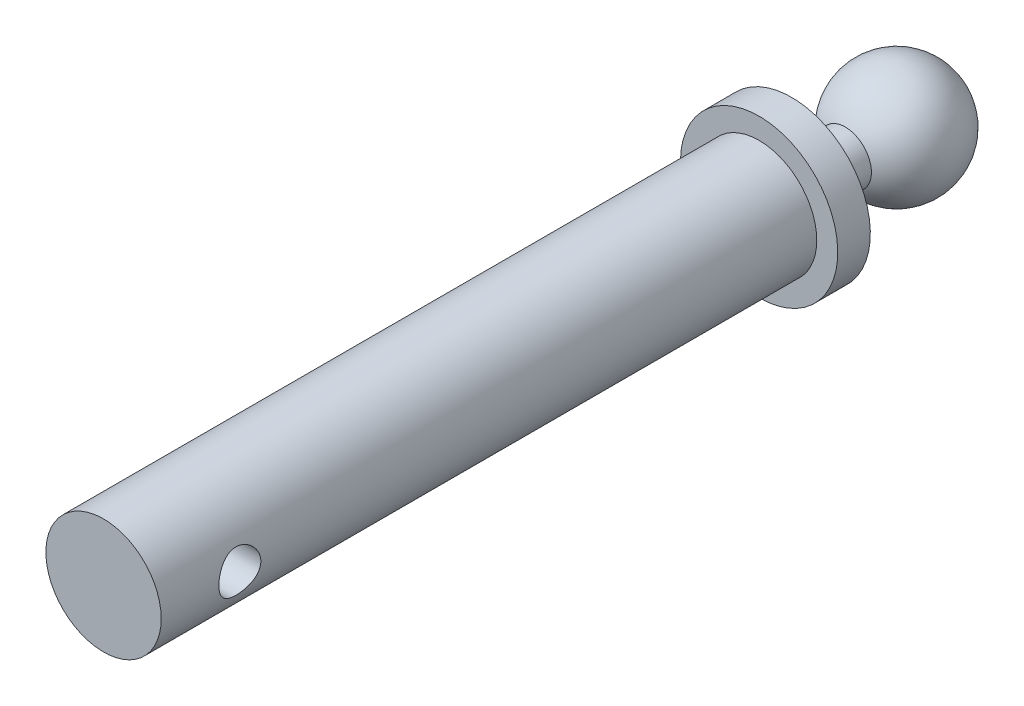
SolidWorks part; units mm, degrees
ref_plane "Plano frontal" through (0, 0, 0) normal (0, 0, 1) x (1, 0, 0)
ref_plane "Plano superior" through (0, 0, 0) normal (0, 1, 0) x (1, 0, 0)
ref_plane "Plano direito" through (0, 0, 0) normal (1, 0, 0) x (0, 0, -1)
sketch "Esboço1" plane through (0, 0, 0) normal (0, 0, 1) x (1, 0, 0)
  line L0 (-15.9999, 0) -> (15.9999, 0) construction
  circle A1 centre (15.9999, 0) radius 5.4973
  dimension "D2" = 10.9947
  dimension "D3" = 15.9999
extrude "Ressalto-extrusão1" add sketch "Esboço1" along normal blind 60 and the other way blind 15
sketch "Esboço2" plane through (0, 0, 0) normal (1, 0, 0) x (0, 0, -1)
  line L0 (-60, 5.4973) -> (-60, -5.4973) construction
  circle A0 centre (-60, 0) radius 4
  dimension "D1" = 8
extrude "Corte-extrusão1" cut sketch "Esboço2" against normal blind 71 and the other way blind 71
sketch "Esboço8" plane through (0, 0, 0) normal (1, 0, 0) x (0, 0, -1)
  circle A2 centre (-52, 0) radius 2
extrude "Corte-extrusão3" cut sketch "Esboço8" along normal through all and the other way through all
sketch "Esboço9" plane through (0, 0, -15) normal (0, 0, -1) x (-1, 0, 0)
  circle A0 centre (-15.9999, 0) radius 7.5
  circle A1 centre (-15.9999, 0) radius 5.4973
  circle A2 centre (-15.9999, 0) radius 5.4973
  dimension "D2" = 15
  dimension "D1" = 0
extrude "Ressalto-extrusão5" add sketch "Esboço9" along normal blind 4 from offset 12 offset against normal yes
sketch "Esboço11" plane through (0, 0, 0) normal (1, 0, 0) x (0, 0, -1)
  line L0 (-56, 0) -> (-56, 5.4973)
  line L1 (-56, 5.4973) -> (-56, -5.4973)
  line L2 (-60, 4) -> (-60, -5.4973)
  line L3 (-60, 5.4973) -> (-60, 4) construction
  line L4 (-60, -5.4973) -> (-60, 5.4973)
  line L5 (-60, -5.4973) -> (3, -5.4973) construction
  line L6 (3, 5.4973) -> (-60, 5.4973) construction
  line L7 (-60, -5.4973) -> (-56, -5.4973)
  line L8 (-56, 5.4973) -> (-60, 5.4973)
  arc A0 (-60, -4) -> (-60, 4) centre (-60, 0) ccw construction
extrude "Corte-extrusão5" cut sketch "Esboço11" along normal through all contours L0 L8 L4 L2 L7 L1 region at (0, 0, 58)
sketch "Esboço12" plane through (0, 0, 56) normal (0, 0, 1) x (1, 0, 0)
  circle A1 centre (15.9999, 0) radius 5.4973
  circle A2 centre (15.9999, 0) radius 5.4973
  dimension "D1" = 0
extrude "Ressalto-extrusão6" add sketch "Esboço12" along normal blind 3.5
sketch "Esboço14" plane through (0, 0, -15) normal (0, 0, -1) x (-1, 0, 0)
  circle A1 centre (-15.9999, 0) radius 5.4973
  circle A2 centre (-15.9999, 0) radius 5.4973
  circle M2 centre (-15.9999, 0) radius 5.4973
  dimension "D1" = 0
extrude "Ressalto-extrusão7" add sketch "Esboço14" along normal blind 6 contours M2 region at (15.9999, 0, -15)
sketch "Esboço16" plane through (0, 0, 0) normal (1, 0, 0) x (0, 0, -1)
  line L1 (-18.895, 5.4973) -> (-18.895, -21.1472) construction
  circle A0 centre (-52, 0) radius 2 construction
  circle A2 centre (14.21, 0) radius 2
  dimension "D1" = 14.21
extrude "Corte-extrusão7" cut sketch "Esboço16" along normal through all and the other way through all
sketch "Esboço17" plane through (0, 0, 0) normal (1, 0, 0) x (0, 0, -1)
  line L0 (19.21, -9.1624) -> (19.21, -5.1185)
  line L1 (9.21, -5.1185) -> (9.21, -9.1624)
  line L2 (9.21, -9.1624) -> (19.21, -9.1624)
  line L3 (19.21, -5.1185) -> (19.21, 5.1185)
  line L4 (9.21, 5.1185) -> (9.21, -5.1185)
  line L5 (19.21, 5.1185) -> (19.21, 9.4973)
  line L6 (19.21, 5.1185) -> (9.21, 5.1185)
  line L7 (9.21, 9.4973) -> (9.21, 5.1185)
  line L8 (19.21, 9.4973) -> (9.21, 9.4973)
  line L9 (9.21, -5.1185) -> (19.21, -5.1185)
  line L10 (9.21, 0) -> (19.21, 0)
  dimension "D1" = 9.21
  dimension "D2" = 9.21
  dimension "D3" = 19.21
  dimension "D4" = 19.21
  dimension "D5" = 5.1185
  dimension "D6" = 9.4973
  dimension "D7" = 9.4973
  dimension "D8" = 5.1185
  dimension "D11" = 9.1624
  dimension "D12" = 9.1624
extrude "Corte-extrusão8" cut sketch "Esboço17" against normal through all and the other way through all contours L10 L4 L9 L3 | L4 L10 L3 L6 region at (0, -2.5593, -14.21) region at (0, 2.5593, -14.21)
sketch "Esboço18" plane through (0, 0, -21) normal (0, 0, -1) x (-1, 0, 0)
  line L0 (-18.0052, 5.1185) -> (-21.4817, 5.1185)
  line L1 (-21.4817, 5.1185) -> (-10.5181, 5.1185)
  line L2 (-18.0052, -5.1185) -> (-13.9946, -5.1185)
  line L3 (-13.9946, 5.1185) -> (-18.0052, 5.1185)
  line L4 (-18.0052, -5.1185) -> (-13.9946, -5.1185)
  line L5 (-13.9946, 5.1185) -> (-18.0052, 5.1185)
  line L6 (-18.0052, -5.1185) -> (-21.4817, -5.1185)
  line L7 (-21.4817, -5.1185) -> (-10.5181, -5.1185)
  circle A1 centre (-15.9999, 0) radius 7.5
  arc A2 (-13.9946, -5.1185) -> (-13.9946, 5.1185) centre (-15.9999, 0) ccw
  arc A3 (-18.0052, 5.1185) -> (-18.0052, -5.1185) centre (-15.9999, 0) ccw
  arc A4 (-13.9946, -5.1185) -> (-13.9946, 5.1185) centre (-15.9999, 0) ccw
  arc A5 (-18.0052, 5.1185) -> (-18.0052, -5.1185) centre (-15.9999, 0) ccw
  circle A6 centre (-15.9999, 0) radius 7.5
  circle M6 centre (-15.9999, 0) radius 5.4973
  dimension "D1" = 0
  dimension "D2" = 0
extrude "Ressalto-extrusão8" add sketch "Esboço18" against normal up to surface (14 mm away) contours L1 A6 L0 M6 | L6 A6 L7 M6 region at (15.9999, 6.1342, -21) region at (15.9999, -6.1342, -21) up to face at (8.4999, 0, -7)
sketch "Esboço19" plane through (0, 0, -21) normal (0, 0, -1) x (-1, 0, 0)
  line L0 (-10.5181, 5.1185) -> (-13.9946, 5.1185) construction
  line L1 (-13.9946, -5.1185) -> (-10.5181, -5.1185) construction
  line L2 (-21.4817, -5.1185) -> (-18.0052, -5.1185) construction
  line L3 (-18.0052, 5.1185) -> (-21.4817, 5.1185) construction
  line L4 (-10.5181, 5.1185) -> (-13.9946, 5.1185)
  line L5 (-13.9946, -5.1185) -> (-10.5181, -5.1185)
  line L6 (-21.4817, -5.1185) -> (-18.0052, -5.1185)
  line L7 (-18.0052, 5.1185) -> (-21.4817, 5.1185)
  arc A0 (-13.9946, -5.1185) -> (-13.9946, 5.1185) centre (-15.9999, 0) ccw construction
  arc A1 (-18.0052, 5.1185) -> (-18.0052, -5.1185) centre (-15.9999, 0) ccw construction
  arc A2 (-13.9946, -5.1185) -> (-13.9946, 5.1185) centre (-15.9999, 0) ccw
  arc A3 (-18.0052, 5.1185) -> (-18.0052, -5.1185) centre (-15.9999, 0) ccw
  arc A4 (-10.5181, -5.1185) -> (-10.5181, 5.1185) centre (-15.9999, 0) ccw construction
  arc A5 (-21.4817, 5.1185) -> (-21.4817, -5.1185) centre (-15.9999, 0) ccw construction
  arc A6 (-10.5181, -5.1185) -> (-10.5181, 5.1185) centre (-15.9999, 0) ccw
  arc A7 (-21.4817, 5.1185) -> (-21.4817, -5.1185) centre (-15.9999, 0) ccw
  arc M1 (-13.9946, -5.1185) -> (-13.9946, 5.1185) centre (-15.9999, 0) ccw
  line M2 (-13.9946, 5.1185) -> (-10.5181, 5.1185)
  line M4 (-21.4817, 5.1185) -> (-18.0052, 5.1185)
  arc M5 (-18.0052, 5.1185) -> (-18.0052, -5.1185) centre (-15.9999, 0) ccw
  line M6 (-18.0052, -5.1185) -> (-21.4817, -5.1185)
  line M8 (-10.5181, -5.1185) -> (-13.9946, -5.1185)
extrude "Ressalto-extrusão9" add sketch "Esboço19" against normal up to vertex (1.79 mm away) contours A7 M4 M6 M5 | A6 M8 M2 M1 region at (10.416, 0, -21) region at (21.5838, 0, -21) up to point (18.0052, 5.1185, -19.21)
sketch "Esboço20" plane through (0, 0, -7) normal (0, 0, -1) x (-1, 0, 0)
  line L0 (-10.5181, 5.1185) -> (-13.9946, 5.1185) construction
  line L1 (-13.9946, -5.1185) -> (-10.5181, -5.1185) construction
  line L2 (-18.0052, 5.1185) -> (-21.4817, 5.1185) construction
  line L3 (-21.4817, -5.1185) -> (-18.0052, -5.1185) construction
  line L4 (-10.5181, 5.1185) -> (-13.9946, 5.1185)
  line L5 (-13.9946, -5.1185) -> (-10.5181, -5.1185)
  line L6 (-18.0052, 5.1185) -> (-21.4817, 5.1185)
  line L7 (-21.4817, -5.1185) -> (-18.0052, -5.1185)
  arc A0 (-13.9946, -5.1185) -> (-13.9946, 5.1185) centre (-15.9999, 0) ccw construction
  arc A1 (-10.5181, -5.1185) -> (-10.5181, 5.1185) centre (-15.9999, 0) ccw construction
  arc A2 (-18.0052, 5.1185) -> (-18.0052, -5.1185) centre (-15.9999, 0) ccw construction
  arc A3 (-21.4817, 5.1185) -> (-21.4817, -5.1185) centre (-15.9999, 0) ccw construction
  arc A4 (-13.9946, -5.1185) -> (-13.9946, 5.1185) centre (-15.9999, 0) ccw
  arc A5 (-10.5181, -5.1185) -> (-10.5181, 5.1185) centre (-15.9999, 0) ccw
  arc A6 (-18.0052, 5.1185) -> (-18.0052, -5.1185) centre (-15.9999, 0) ccw
  arc A7 (-21.4817, 5.1185) -> (-21.4817, -5.1185) centre (-15.9999, 0) ccw
extrude "Ressalto-extrusão10" add sketch "Esboço20" along normal up to vertex (2.21 mm away) up to point (18.0052, 5.1185, -9.21)
sketch "Esboço21" plane through (0, 0, -21) normal (0, 0, -1) x (-1, 0, 0)
  circle A1 centre (-15.9999, 0) radius 7.5
  circle A2 centre (-15.9999, 0) radius 7.5
  dimension "D1" = 0
extrude "Ressalto-extrusão11" add sketch "Esboço21" along normal blind 3
sketch "Esboço22" plane through (0, 5.1185, 0) normal (0, -1, 0) x (1, 0, 0)
  line L0 (23.4999, -6.105) -> (23.4999, -31.541)
  line L1 (23.4999, -9.21) -> (23.4999, -3) construction
  line L2 (23.4999, -6.105) -> (8.4999, -6.105)
  line L5 (8.4999, -6.105) -> (8.4999, -31.541)
  line L6 (8.4999, -31.541) -> (23.4999, -31.541)
extrude "Corte-extrusão9" cut sketch "Esboço22" against normal through all and the other way through all
sketch "Esboço23" plane through (0, 0, -6.105) normal (0, 0, -1) x (-1, 0, 0)
  circle A0 centre (-15.9999, 0) radius 2.5
  dimension "D2" = 5
extrude "Ressalto-extrusão12" add sketch "Esboço23" along normal blind 10
sketch "Esboço24" plane through (0, 0, -16.105) normal (0, 0, -1) x (-1, 0, 0)
  line L0 (-15.9999, 5.4973) -> (-15.9999, -5.4973)
  circle A0 centre (-15.9999, 0) radius 5.4973 construction
  arc A1 (-15.9999, 5.4973) -> (-15.9999, -5.4973) centre (-15.9999, 0) ccw
revolve "Revolução1" add sketch "Esboço24" angle 360 about L0
